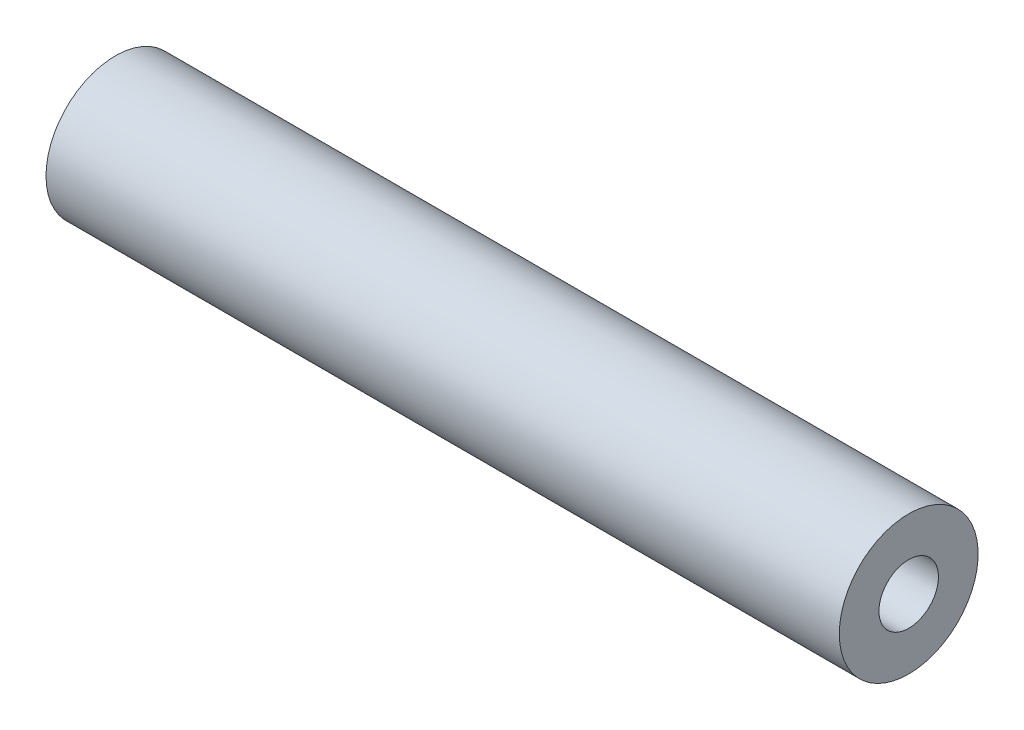
SolidWorks part; units mm, degrees
ref_plane "Front Plane" through (0, 0, 0) normal (0, 0, 1) x (1, 0, 0)
ref_plane "Top Plane" through (0, 0, 0) normal (0, 1, 0) x (1, 0, 0)
ref_plane "Right Plane" through (0, 0, 0) normal (1, 0, 0) x (0, 0, -1)
sketch "Sketch1" plane through (0, 0, 0) normal (0, 0, 1) x (1, 0, 0)
  line L0 (0, 0) -> (240, 0) construction
  line L1 (20, 7.5) -> (220, 7.5)
  line L6 (20, 17.5) -> (220, 17.5)
  line L7 (20, 17.5) -> (20, 7.5)
  line L9 (220, 17.5) -> (220, 7.5)
  dimension "L" = 240
  dimension "D_s" = 15
  dimension "D" = 35
revolve "Revolve1" add sketch "Sketch1" angle 360 about L0
